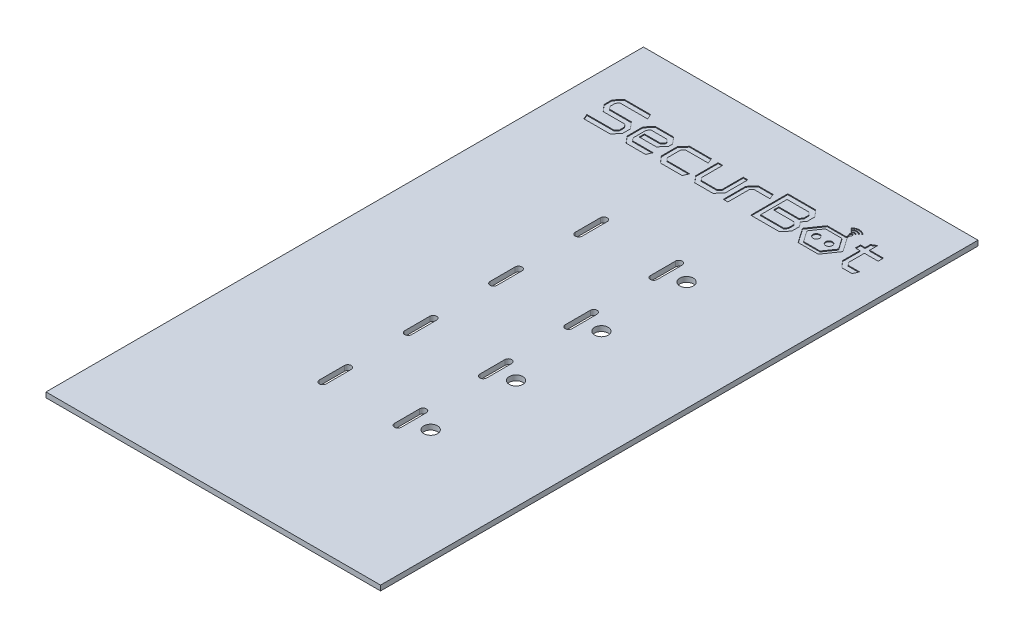
SolidWorks part; units mm, degrees
ref_plane "Front Plane" through (0, 0, 0) normal (0, 0, 1) x (1, 0, 0)
ref_plane "Top Plane" through (0, 0, 0) normal (0, 1, 0) x (1, 0, 0)
ref_plane "Right Plane" through (0, 0, 0) normal (1, 0, 0) x (0, 0, -1)
sketch "Sketch1" plane through (0, 0, 0) normal (0, 1, 0) x (1, 0, 0)
  line L1 (0, 0) -> (196, 0)
  line L2 (0, 0) -> (0, 350)
  line L3 (0, 350) -> (196, 350)
  line L4 (196, 0) -> (196, 350)
  dimension "D1" = 350
  dimension "D2" = 196
extrude "Boss-Extrude1" add sketch "Sketch1" along normal blind 3
hole_wizard "Ø8.0mm Dowel Hole1" positions "Sketch2" profile "Sketch3" hole size "Ø8.0" standard "AS" end condition up to next
sketch "Sketch2" plane through (0, 0, 0) normal (0, -1, 0) x (-1, 0, 0)
  point P0 (-131.875, 93.5)
  point P3 (-131.875, 143.5)
  point P6 (-131.875, 193.5067)
  point P9 (-131.875, 243.4059)
sketch "Sketch3" plane through (131.875, 0, -93.5) normal (1, 0, 0) x (0, 0, -1)
  line L0 (0, 0) -> (0, 3)
  line L1 (0, 3) -> (4, 3)
  line L2 (4, 3) -> (4, 0)
  line L5 (4, 0) -> (0, 0)
  line L11 (0, -6.35) -> (0, 107.95) construction
  dimension "Thru Hole Dia." = 8
  dimension "Thru Hole Depth" = 3
hole_wizard "Ø4.0mm Dowel Slot1" positions "Sketch4" profile "Sketch5" size "Ø4.0" standard "AS" slot yes end condition up to next
sketch "Sketch4" plane through (0, 0, 0) normal (0, -1, 0) x (-1, 0, 0)
  line L0 (-120, 84.15) -> (-120, 102.85) construction
  point P0 (-120, 93.5)
  point P7 (-76, 93.5)
  point P10 (-120, 143.5)
  point P13 (-76, 143.5)
  point P16 (-120, 193.5067)
  point P19 (-76, 193.5067)
  point P22 (-120, 243.4059)
  point P25 (-76, 243.4059)
  dimension "D1" = 18.7
sketch "Sketch5" plane through (120, 0, -93.5) normal (1, 0, 0) x (0, 0, -1)
  line L0 (0, 0) -> (0, 3)
  line L1 (0, 3) -> (2, 3)
  line L2 (2, 3) -> (2, 0)
  line L5 (2, 0) -> (0, 0)
  line L11 (0, -6.35) -> (0, 107.95) construction
  dimension "Thru Hole Dia." = 4
  dimension "Thru Hole Depth" = 3
sketch "Sketch12" plane through (0, 3, 0) normal (0, 1, 0) x (1, 0, 0)
  line L0 (0, 350) -> (0, 300)
  line L1 (0, 350) -> (0, 0) construction
  line L2 (0, 300) -> (98, 300)
sketch "Sketch14" plane through (0, 3, 0) normal (0, 1, 0) x (1, 0, 0)
  line L0 (141.5351, 300.3658) -> (138.5775, 304.6298)
  line L1 (138.5775, 304.6298) -> (141.5351, 308.8937)
  line L2 (141.5351, 308.8937) -> (144.4926, 313.1577)
  line L3 (144.4926, 313.1577) -> (150.0965, 313.1588)
  line L4 (150.0965, 313.1588) -> (155.7003, 313.1599)
  line L5 (155.7003, 313.1599) -> (155.7003, 313.9708)
  line L6 (155.7003, 313.9708) -> (155.7003, 314.7817)
  line L7 (155.7003, 314.7817) -> (155.57, 314.8651)
  line L8 (156.4983, 314.8744) -> (156.3797, 314.8004)
  line L9 (156.3797, 314.8004) -> (156.3787, 313.9527)
  line L10 (156.3787, 313.9527) -> (156.3777, 313.105)
  line L11 (156.3777, 313.105) -> (159.3193, 308.8674)
  line L12 (159.3193, 308.8674) -> (162.261, 304.6298)
  line L13 (162.261, 304.6298) -> (159.3035, 300.3658)
  line L14 (159.3035, 300.3658) -> (156.3459, 296.1018)
  line L15 (156.3459, 296.1018) -> (150.4193, 296.1018)
  line L16 (150.4193, 296.1018) -> (144.4926, 296.1018)
  line L17 (144.4926, 296.1018) -> (141.5351, 300.3658)
  line L18 (157.4604, 307.8365) -> (155.2414, 311.0327)
  line L19 (155.2414, 311.0327) -> (150.4192, 311.0327)
  line L20 (150.4192, 311.0327) -> (145.5971, 311.0327)
  line L21 (145.5971, 311.0327) -> (143.378, 307.8365)
  line L22 (145.4176, 298.4861) -> (145.6066, 298.2162)
  line L23 (145.6066, 298.2162) -> (150.424, 298.2215)
  line L24 (150.424, 298.2215) -> (155.2415, 298.2269)
  line L25 (155.2415, 298.2269) -> (157.4604, 301.423)
  line L26 (25.6857, 299.2375) -> (33.7249, 299.2429)
  line L27 (33.7249, 299.2429) -> (34.3863, 300.0049)
  line L28 (34.3863, 300.0049) -> (35.0477, 300.7669)
  line L29 (35.0477, 300.7669) -> (35.0485, 302.3226)
  line L30 (35.0485, 302.3226) -> (35.0494, 303.8784)
  line L31 (35.0494, 303.8784) -> (34.3778, 304.656)
  line L32 (34.3778, 304.656) -> (33.7062, 305.4336)
  line L33 (33.7062, 305.4336) -> (27.3432, 305.4338)
  line L34 (27.3432, 305.4338) -> (20.9802, 305.4341)
  line L35 (20.9802, 305.4341) -> (19.3052, 307.3737)
  line L36 (19.3052, 307.3737) -> (17.6302, 309.3133)
  line L37 (17.6302, 309.3133) -> (17.6302, 311.6337)
  line L38 (17.6302, 311.6337) -> (17.6302, 313.954)
  line L39 (17.6302, 313.954) -> (19.3065, 315.8959)
  line L40 (19.3065, 315.8959) -> (20.9828, 317.8378)
  line L41 (20.9828, 317.8378) -> (28.6882, 317.8325)
  line L42 (28.6882, 317.8325) -> (36.3936, 317.8272)
  line L43 (36.3936, 317.8272) -> (37.0555, 316.2944)
  line L44 (29.6793, 314.7255) -> (21.6412, 314.7247)
  line L45 (21.6412, 314.7247) -> (20.9802, 313.9582)
  line L46 (20.9802, 313.9582) -> (20.3192, 313.1917)
  line L47 (20.3192, 313.1917) -> (20.3188, 311.6359)
  line L48 (20.3188, 311.6359) -> (20.3183, 310.0801)
  line L49 (20.3183, 310.0801) -> (20.9891, 309.3022)
  line L50 (20.9891, 309.3022) -> (21.6598, 308.5244)
  line L51 (21.6598, 308.5244) -> (28.0228, 308.5244)
  line L52 (28.0228, 308.5244) -> (34.3859, 308.5244)
  line L53 (34.3859, 308.5244) -> (36.0622, 306.5825)
  line L54 (36.0622, 306.5825) -> (37.7385, 304.6405)
  line L55 (37.7385, 304.6405) -> (37.7385, 302.3289)
  line L56 (37.7385, 302.3289) -> (37.7385, 300.0173)
  line L57 (37.7385, 300.0173) -> (37.5956, 299.8478)
  line L58 (35.9182, 297.9002) -> (34.3836, 296.1221)
  line L59 (34.3836, 296.1221) -> (26.6789, 296.1216)
  line L60 (26.6789, 296.1216) -> (18.9742, 296.1211)
  line L61 (18.9742, 296.1211) -> (18.3212, 297.6349)
  line L62 (42.0618, 298.0628) -> (40.3846, 300.0049)
  line L63 (40.3846, 300.0049) -> (40.3844, 304.6529)
  line L64 (40.3844, 304.6529) -> (40.3841, 309.3009)
  line L65 (40.3841, 309.3009) -> (42.0596, 311.241)
  line L66 (42.0596, 311.241) -> (43.7351, 313.1811)
  line L67 (43.7351, 313.1811) -> (49.0967, 313.1811)
  line L68 (49.0967, 313.1811) -> (54.4583, 313.1811)
  line L69 (54.4583, 313.1811) -> (56.1313, 311.2435)
  line L70 (56.1313, 311.2435) -> (57.8043, 309.3058)
  line L71 (57.8043, 309.3058) -> (57.8043, 308.1436)
  line L72 (57.8043, 308.1436) -> (57.8043, 306.9814)
  line L73 (57.8043, 306.9814) -> (56.1313, 305.0436)
  line L74 (56.1313, 305.0436) -> (54.4585, 303.1058)
  line L75 (54.4585, 303.1058) -> (49.4323, 303.1058)
  line L76 (49.4323, 303.1058) -> (44.406, 303.1058)
  line L77 (44.406, 303.1058) -> (44.406, 304.6509)
  line L78 (44.406, 304.6509) -> (44.406, 306.1961)
  line L79 (44.406, 306.1961) -> (49.0917, 306.1961)
  line L80 (49.0917, 306.1961) -> (53.7773, 306.1961)
  line L81 (53.7773, 306.1961) -> (54.4468, 306.9717)
  line L82 (54.4468, 306.9717) -> (55.1163, 307.7472)
  line L83 (55.1163, 307.7472) -> (55.1163, 308.1432)
  line L84 (55.1163, 308.1432) -> (55.1163, 308.5392)
  line L85 (55.1163, 308.5392) -> (54.4476, 309.315)
  line L86 (54.4476, 309.315) -> (53.7788, 310.0908)
  line L87 (53.7788, 310.0908) -> (49.0969, 310.0908)
  line L88 (49.0969, 310.0908) -> (44.4149, 310.0908)
  line L89 (44.4149, 310.0908) -> (43.7438, 309.3129)
  line L90 (43.7438, 309.3129) -> (43.0727, 308.535)
  line L91 (43.0727, 308.535) -> (43.0733, 304.6509)
  line L92 (43.0733, 304.6509) -> (43.0738, 300.7669)
  line L93 (43.0738, 300.7669) -> (43.7346, 300.0005)
  line L94 (43.7346, 300.0005) -> (44.3954, 299.2341)
  line L95 (44.3954, 299.2341) -> (50.4251, 299.2332)
  line L96 (55.781, 297.6394) -> (55.1269, 296.1217)
  line L97 (55.1269, 296.1217) -> (49.4329, 296.1212)
  line L98 (49.4329, 296.1212) -> (43.739, 296.1208)
  line L99 (43.739, 296.1208) -> (42.0618, 298.0628)
  line L100 (62.1701, 298.0628) -> (60.4929, 300.0049)
  line L101 (60.4929, 300.0049) -> (60.4927, 304.6529)
  line L102 (60.4927, 304.6529) -> (60.4925, 309.3009)
  line L103 (60.4925, 309.3009) -> (62.168, 311.241)
  line L104 (62.168, 311.241) -> (63.8435, 313.1811)
  line L105 (63.8435, 313.1811) -> (70.2086, 313.1811)
  line L106 (70.2086, 313.1811) -> (76.5737, 313.1811)
  line L107 (76.5737, 313.1811) -> (76.9094, 312.4032)
  line L108 (77.5745, 310.8634) -> (77.9041, 310.1014)
  line L109 (77.9041, 310.1014) -> (71.2091, 310.0908)
  line L110 (71.2091, 310.0908) -> (64.5142, 310.0802)
  line L111 (64.5142, 310.0802) -> (63.8475, 309.3076)
  line L112 (63.8475, 309.3076) -> (63.1808, 308.535)
  line L113 (63.1808, 308.535) -> (63.1814, 304.6509)
  line L114 (63.1814, 304.6509) -> (63.1819, 300.7669)
  line L115 (63.1819, 300.7669) -> (63.8428, 300.0005)
  line L116 (63.8428, 300.0005) -> (64.5036, 299.2341)
  line L117 (64.5036, 299.2341) -> (71.1975, 299.2332)
  line L118 (77.232, 297.6501) -> (76.5721, 296.1208)
  line L119 (76.5721, 296.1208) -> (70.2096, 296.1208)
  line L120 (70.2096, 296.1208) -> (63.8471, 296.1208)
  line L121 (63.8471, 296.1208) -> (62.1701, 298.0628)
  line L122 (82.2567, 298.0626) -> (80.5798, 300.0044)
  line L123 (80.5798, 300.0044) -> (80.5798, 306.5928)
  line L124 (80.5798, 306.5928) -> (80.5798, 313.1811)
  line L125 (80.5798, 313.1811) -> (81.9239, 313.1811)
  line L126 (81.9239, 313.1811) -> (83.268, 313.1811)
  line L127 (83.268, 313.1811) -> (83.268, 306.9793)
  line L128 (83.268, 306.9793) -> (83.268, 300.7775)
  line L129 (83.268, 300.7775) -> (83.9367, 300.0048)
  line L130 (83.9367, 300.0048) -> (84.6053, 299.2322)
  line L131 (84.6053, 299.2322) -> (89.2967, 299.2375)
  line L132 (89.2967, 299.2375) -> (93.9881, 299.2429)
  line L133 (93.9881, 299.2429) -> (94.649, 300.0049)
  line L134 (94.649, 300.0049) -> (95.3099, 300.7669)
  line L135 (95.3099, 300.7669) -> (95.3109, 306.974)
  line L136 (95.3109, 306.974) -> (95.3118, 313.1811)
  line L137 (95.3118, 313.1811) -> (96.6559, 313.1811)
  line L138 (96.6559, 313.1811) -> (98, 313.1811)
  line L139 (98, 313.1811) -> (98, 306.5906)
  line L140 (98, 306.5906) -> (98, 300)
  line L141 (98, 300) -> (96.325, 298.0604)
  line L142 (96.325, 298.0604) -> (94.65, 296.1208)
  line L143 (94.65, 296.1208) -> (89.2918, 296.1208)
  line L144 (89.2918, 296.1208) -> (83.9336, 296.1208)
  line L145 (83.9336, 296.1208) -> (82.2567, 298.0626)
  line L146 (100.667, 302.7108) -> (100.667, 309.3009)
  line L147 (100.667, 309.3009) -> (102.3425, 311.2411)
  line L148 (102.3425, 311.2411) -> (104.0181, 313.1812)
  line L149 (104.0181, 313.1812) -> (108.3761, 313.1759)
  line L150 (108.3761, 313.1759) -> (112.7341, 313.1705)
  line L151 (112.7341, 313.1705) -> (113.3969, 311.6359)
  line L152 (113.3969, 311.6359) -> (114.0596, 310.1014)
  line L153 (114.0596, 310.1014) -> (109.3741, 310.0908)
  line L154 (109.3741, 310.0908) -> (104.6887, 310.0802)
  line L155 (104.6887, 310.0802) -> (104.022, 309.3076)
  line L156 (104.022, 309.3076) -> (103.3554, 308.535)
  line L157 (103.3554, 308.535) -> (103.3554, 302.3279)
  line L158 (103.3554, 302.3279) -> (103.3554, 296.1208)
  line L159 (103.3554, 296.1208) -> (102.0113, 296.1208)
  line L160 (102.0113, 296.1208) -> (100.6672, 296.1208)
  line L161 (100.6672, 296.1208) -> (100.667, 302.7108)
  line L162 (116.7325, 306.9793) -> (116.7325, 317.8378)
  line L163 (116.7325, 317.8378) -> (124.9081, 317.8372)
  line L164 (124.9081, 317.8372) -> (133.0837, 317.8366)
  line L165 (133.0837, 317.8366) -> (134.6183, 316.0585)
  line L166 (136.2958, 314.1109) -> (136.4387, 313.9413)
  line L167 (136.4387, 313.9413) -> (136.4387, 311.6294)
  line L168 (136.4387, 311.6294) -> (136.4387, 309.3175)
  line L169 (136.4387, 309.3175) -> (135.5391, 308.2762)
  line L170 (135.7402, 305.9153) -> (136.8408, 304.6411)
  line L171 (136.8408, 304.6411) -> (136.8408, 302.3292)
  line L172 (136.8408, 302.3292) -> (136.8408, 300.0173)
  line L173 (136.8408, 300.0173) -> (136.698, 299.8478)
  line L174 (135.0205, 297.9001) -> (133.4859, 296.122)
  line L175 (133.4859, 296.122) -> (125.1092, 296.1214)
  line L176 (125.1092, 296.1214) -> (116.7325, 296.1208)
  line L177 (116.7325, 296.1208) -> (116.7325, 306.9793)
  line L178 (133.4822, 300.0084) -> (134.1527, 300.7846)
  line L179 (134.1527, 300.7846) -> (134.1527, 302.3332)
  line L180 (134.1527, 302.3332) -> (134.1527, 303.8818)
  line L181 (134.1527, 303.8818) -> (133.4822, 304.658)
  line L182 (133.4822, 304.658) -> (132.8118, 305.4341)
  line L183 (132.8118, 305.4341) -> (126.783, 305.4341)
  line L184 (126.783, 305.4341) -> (120.7542, 305.4341)
  line L185 (120.7542, 305.4341) -> (120.7542, 306.9899)
  line L186 (120.7542, 306.9899) -> (120.7542, 308.5456)
  line L187 (120.7542, 308.5456) -> (126.5819, 308.5456)
  line L188 (126.5819, 308.5456) -> (132.4097, 308.5456)
  line L189 (132.4097, 308.5456) -> (133.0801, 309.3195)
  line L190 (133.0801, 309.3195) -> (133.7505, 310.0934)
  line L191 (133.7505, 310.0934) -> (133.7505, 311.6359)
  line L192 (133.7505, 311.6359) -> (133.7505, 313.1785)
  line L193 (133.7505, 313.1785) -> (133.0801, 313.9524)
  line L194 (133.0801, 313.9524) -> (132.4097, 314.7263)
  line L195 (132.4097, 314.7263) -> (125.9152, 314.7263)
  line L196 (125.9152, 314.7263) -> (119.4207, 314.7263)
  line L197 (119.4207, 314.7263) -> (119.4207, 306.9793)
  line L198 (119.4207, 306.9793) -> (119.4207, 299.2323)
  line L199 (119.4207, 299.2323) -> (126.1162, 299.2323)
  line L200 (126.1162, 299.2323) -> (132.8118, 299.2323)
  line L201 (132.8118, 299.2323) -> (133.4822, 300.0084)
  line L202 (168.3797, 298.0577) -> (166.707, 299.9947)
  line L203 (166.707, 299.9947) -> (166.707, 305.0427)
  line L204 (166.707, 305.0427) -> (166.707, 310.0908)
  line L205 (166.707, 310.0908) -> (165.3629, 310.0908)
  line L206 (165.3629, 310.0908) -> (164.0188, 310.0908)
  line L207 (164.0188, 310.0908) -> (164.0188, 311.6359)
  line L208 (164.0188, 311.6359) -> (164.0188, 313.1811)
  line L209 (164.0188, 313.1811) -> (165.3628, 313.1811)
  line L210 (165.3628, 313.1811) -> (166.7067, 313.1811)
  line L211 (166.7067, 313.1811) -> (166.7122, 314.7383)
  line L212 (166.7122, 314.7383) -> (166.7176, 316.2955)
  line L213 (166.7176, 316.2955) -> (168.0405, 317.062)
  line L214 (168.0405, 317.062) -> (169.3634, 317.8285)
  line L215 (169.3634, 317.8285) -> (169.374, 315.5101)
  line L216 (169.374, 315.5101) -> (169.3846, 313.1917)
  line L217 (169.3846, 313.1917) -> (173.401, 313.1863)
  line L218 (173.401, 313.1863) -> (177.4173, 313.181)
  line L219 (177.4173, 313.181) -> (177.4173, 311.6359)
  line L220 (177.4173, 311.6359) -> (177.4173, 310.0909)
  line L221 (177.4173, 310.0909) -> (173.401, 310.0855)
  line L222 (173.401, 310.0855) -> (169.3846, 310.0802)
  line L223 (169.3846, 310.0802) -> (169.3792, 305.433)
  line L224 (169.3792, 305.433) -> (169.3739, 300.7859)
  line L225 (169.3739, 300.7859) -> (170.0439, 300.0091)
  line L226 (170.0439, 300.0091) -> (170.7139, 299.2323)
  line L227 (170.7139, 299.2323) -> (174.0679, 299.2323)
  line L228 (176.1037, 296.179) -> (176.077, 296.1208)
  line L229 (176.077, 296.1208) -> (173.0647, 296.1208)
  line L230 (173.0647, 296.1208) -> (170.0524, 296.1208)
  line L231 (170.0524, 296.1208) -> (168.3797, 298.0577)
  line L232 (154.6149, 316.8806) -> (154.43, 317.0664)
  line L233 (154.43, 317.0664) -> (154.5519, 317.1695)
  line L234 (157.3633, 316.8879) -> (157.1848, 316.7132)
  line L235 (157.1848, 316.7132) -> (157.0723, 316.8048)
  line L236 (153.5958, 317.8997) -> (153.4111, 318.0853)
  line L237 (153.4111, 318.0853) -> (153.545, 318.2068)
  line L238 (158.5461, 318.1569) -> (158.5873, 318.111)
  line L239 (158.5873, 318.111) -> (158.4043, 317.928)
  line L240 (158.4043, 317.928) -> (158.2213, 317.7449)
  line L241 (158.2213, 317.7449) -> (158.0967, 317.8533)
  line L242 (153.952, 317.8626) -> (153.7806, 317.7141)
  line L243 (153.7806, 317.7141) -> (153.5958, 317.8997)
  line L244 (152.6528, 318.8428) -> (152.4742, 319.0222)
  line L245 (152.4742, 319.0222) -> (152.5368, 319.0884)
  line L246 (159.4985, 319.1096) -> (159.5395, 319.0638)
  line L247 (159.5395, 319.0638) -> (159.3614, 318.8847)
  spline S0 degree 3 poles (155.57, 314.8651) (155.3342, 315.0161) (155.1712, 315.3097) (155.1712, 315.5835) knots 0 0 0 0 1 1 1 1
  spline S1 degree 3 poles (155.1712, 315.5835) (155.1712, 316.1418) (155.7342, 316.5632) (156.2647, 316.4021) knots 0 0 0 0 1 1 1 1
  spline S2 degree 3 poles (156.2647, 316.4021) (156.6262, 316.2923) (156.8857, 315.9503) (156.8857, 315.5839) knots 0 0 0 0 1 1 1 1
  spline S3 degree 3 poles (156.8857, 315.5839) (156.8857, 315.3149) (156.7212, 315.0137) (156.4983, 314.8744) knots 0 0 0 0 1 1 1 1
  spline S4 degree 3 poles (157.4604, 301.423) (158.6809, 303.1809) (159.6794, 304.624) (159.6794, 304.6298) knots 0 0 0 0 1 1 1 1
  spline S5 degree 3 poles (159.6794, 304.6298) (159.6794, 304.6356) (158.6808, 306.0786) (157.4604, 307.8365) knots 0 0 0 0 1 1 1 1
  spline S6 degree 3 poles (143.378, 307.8365) (142.1575, 306.0786) (141.1626, 304.6305) (141.167, 304.6185) knots 0 0 0 0 1 1 1 1
  spline S7 degree 3 poles (141.167, 304.6185) (141.1738, 304.6001) (144.8409, 299.3095) (145.4176, 298.4861) knots 0 0 0 0 1 1 1 1
  spline S8 degree 3 poles (146.4611, 302.6325) (145.9965, 302.706) (145.6379, 302.8809) (145.3216, 303.1881) knots 0 0 0 0 1 1 1 1
  spline S9 degree 3 poles (145.3216, 303.1881) (145.0489, 303.4529) (144.8651, 303.7713) (144.7739, 304.1366) knots 0 0 0 0 1 1 1 1
  spline S10 degree 3 poles (144.7739, 304.1366) (144.7374, 304.2824) (144.7273, 304.3849) (144.7273, 304.6086) knots 0 0 0 0 1 1 1 1
  spline S11 degree 3 poles (144.7273, 304.6086) (144.7273, 305.0332) (144.8186, 305.3491) (145.0426, 305.6999) knots 0 0 0 0 1 1 1 1
  spline S12 degree 3 poles (145.0426, 305.6999) (145.1515, 305.8704) (145.4143, 306.1369) (145.5867, 306.2516) knots 0 0 0 0 1 1 1 1
  spline S13 degree 3 poles (145.5867, 306.2516) (145.9421, 306.4881) (146.2688, 306.5858) (146.7045, 306.5858) knots 0 0 0 0 1 1 1 1
  spline S14 degree 3 poles (146.7045, 306.5858) (147.1291, 306.5858) (147.445, 306.4945) (147.7958, 306.2705) knots 0 0 0 0 1 1 1 1
  spline S15 degree 3 poles (147.7958, 306.2705) (147.9663, 306.1616) (148.2328, 305.8988) (148.3475, 305.7264) knots 0 0 0 0 1 1 1 1
  spline S16 degree 3 poles (148.3475, 305.7264) (148.584, 305.3711) (148.6817, 305.0443) (148.6817, 304.6086) knots 0 0 0 0 1 1 1 1
  spline S17 degree 3 poles (148.6817, 304.6086) (148.6817, 304.3849) (148.6716, 304.2824) (148.6351, 304.1366) knots 0 0 0 0 1 1 1 1
  spline S18 degree 3 poles (148.6351, 304.1366) (148.5439, 303.7713) (148.3601, 303.4529) (148.0874, 303.1881) knots 0 0 0 0 1 1 1 1
  spline S19 degree 3 poles (148.0874, 303.1881) (147.7146, 302.8261) (147.2914, 302.6471) (146.768, 302.6303) knots 0 0 0 0 1 1 1 1
  spline S20 degree 3 poles (146.768, 302.6303) (146.6341, 302.6259) (146.496, 302.6269) (146.4611, 302.6325) knots 0 0 0 0 1 1 1 1
  spline S21 degree 3 poles (153.8694, 302.6325) (153.4049, 302.706) (153.0463, 302.8809) (152.7299, 303.1881) knots 0 0 0 0 1 1 1 1
  spline S22 degree 3 poles (152.7299, 303.1881) (152.4573, 303.4529) (152.2734, 303.7713) (152.1822, 304.1366) knots 0 0 0 0 1 1 1 1
  spline S23 degree 3 poles (152.1822, 304.1366) (152.1458, 304.2824) (152.1357, 304.3849) (152.1357, 304.6086) knots 0 0 0 0 1 1 1 1
  spline S24 degree 3 poles (152.1357, 304.6086) (152.1357, 305.0332) (152.2269, 305.3491) (152.451, 305.6999) knots 0 0 0 0 1 1 1 1
  spline S25 degree 3 poles (152.451, 305.6999) (152.5599, 305.8704) (152.8226, 306.1369) (152.9951, 306.2516) knots 0 0 0 0 1 1 1 1
  spline S26 degree 3 poles (152.9951, 306.2516) (153.3504, 306.4881) (153.6772, 306.5858) (154.1128, 306.5858) knots 0 0 0 0 1 1 1 1
  spline S27 degree 3 poles (154.1128, 306.5858) (154.5492, 306.5858) (154.8748, 306.4883) (155.2325, 306.2505) knots 0 0 0 0 1 1 1 1
  spline S28 degree 3 poles (155.2325, 306.2505) (155.4006, 306.1387) (155.6685, 305.8657) (155.778, 305.6945) knots 0 0 0 0 1 1 1 1
  spline S29 degree 3 poles (155.778, 305.6945) (155.9983, 305.3501) (156.09, 305.031) (156.09, 304.6086) knots 0 0 0 0 1 1 1 1
  spline S30 degree 3 poles (156.09, 304.6086) (156.09, 304.3849) (156.0799, 304.2824) (156.0435, 304.1366) knots 0 0 0 0 1 1 1 1
  spline S31 degree 3 poles (156.0435, 304.1366) (155.9522, 303.7713) (155.7684, 303.4529) (155.4958, 303.1881) knots 0 0 0 0 1 1 1 1
  spline S32 degree 3 poles (155.4958, 303.1881) (155.1229, 302.8261) (154.6998, 302.6471) (154.1763, 302.6303) knots 0 0 0 0 1 1 1 1
  spline S33 degree 3 poles (154.1763, 302.6303) (154.0425, 302.6259) (153.9043, 302.6269) (153.8694, 302.6325) knots 0 0 0 0 1 1 1 1
  spline S34 degree 3 poles (18.3212, 297.6349) (17.9621, 298.4676) (17.6633, 299.1676) (17.6573, 299.1905) knots 0 0 0 0 1 1 1 1
  spline S35 degree 3 poles (17.6573, 299.1905) (17.6465, 299.232) (17.6975, 299.2323) (25.6857, 299.2375) knots 0 0 0 0 1 1 1 1
  spline S36 degree 3 poles (37.0555, 316.2944) (37.4195, 315.4514) (37.7173, 314.7537) (37.7173, 314.7439) knots 0 0 0 0 1 1 1 1
  spline S37 degree 3 poles (37.7173, 314.7439) (37.7173, 314.7342) (34.1002, 314.7259) (29.6793, 314.7255) knots 0 0 0 0 1 1 1 1
  spline S38 degree 3 poles (37.5956, 299.8478) (37.517, 299.7546) (36.7622, 298.8781) (35.9182, 297.9002) knots 0 0 0 0 1 1 1 1
  spline S39 degree 3 poles (50.4251, 299.2332) (56.1869, 299.2323) (56.4544, 299.2306) (56.445, 299.1947) knots 0 0 0 0 1 1 1 1
  spline S40 degree 3 poles (56.445, 299.1947) (56.4396, 299.1741) (56.1408, 298.4742) (55.781, 297.6394) knots 0 0 0 0 1 1 1 1
  spline S41 degree 3 poles (76.9094, 312.4032) (77.094, 311.9754) (77.3933, 311.2825) (77.5745, 310.8634) knots 0 0 0 0 1 1 1 1
  spline S42 degree 3 poles (71.1975, 299.2332) (76.538, 299.2325) (77.8915, 299.2269) (77.8917, 299.2058) knots 0 0 0 0 1 1 1 1
  spline S43 degree 3 poles (77.8917, 299.2058) (77.8917, 299.1913) (77.5949, 298.4912) (77.232, 297.6501) knots 0 0 0 0 1 1 1 1
  spline S44 degree 3 poles (134.6183, 316.0585) (135.4624, 315.0806) (136.2172, 314.2041) (136.2958, 314.1109) knots 0 0 0 0 1 1 1 1
  spline S45 degree 3 poles (135.5391, 308.2762) (135.0443, 307.7034) (134.6395, 307.2246) (134.6395, 307.2122) knots 0 0 0 0 1 1 1 1
  spline S46 degree 3 poles (134.6395, 307.2122) (134.6395, 307.1997) (135.1348, 306.6161) (135.7402, 305.9153) knots 0 0 0 0 1 1 1 1
  spline S47 degree 3 poles (136.698, 299.8478) (136.6194, 299.7546) (135.8645, 298.8781) (135.0205, 297.9001) knots 0 0 0 0 1 1 1 1
  spline S48 degree 3 poles (174.0679, 299.2323) (176.7426, 299.2323) (177.4197, 299.2269) (177.4113, 299.2058) knots 0 0 0 0 1 1 1 1
  spline S49 degree 3 poles (177.4113, 299.2058) (177.393, 299.1598) (176.1316, 296.2399) (176.1037, 296.179) knots 0 0 0 0 1 1 1 1
  spline S50 degree 3 poles (154.5519, 317.1695) (154.8096, 317.3874) (155.1268, 317.5518) (155.4631, 317.6415) knots 0 0 0 0 1 1 1 1
  spline S51 degree 3 poles (155.4631, 317.6415) (155.6435, 317.6896) (155.7099, 317.6963) (156.0072, 317.6963) knots 0 0 0 0 1 1 1 1
  spline S52 degree 3 poles (156.0072, 317.6963) (156.3046, 317.6963) (156.371, 317.6896) (156.5514, 317.6415) knots 0 0 0 0 1 1 1 1
  spline S53 degree 3 poles (156.5514, 317.6415) (156.7924, 317.5772) (157.0642, 317.4544) (157.2627, 317.3202) knots 0 0 0 0 1 1 1 1
  spline S54 degree 3 poles (157.2627, 317.3202) (157.4154, 317.217) (157.5418, 317.1082) (157.5418, 317.08) knots 0 0 0 0 1 1 1 1
  spline S55 degree 3 poles (157.5418, 317.08) (157.5418, 317.0704) (157.4615, 316.9839) (157.3633, 316.8879) knots 0 0 0 0 1 1 1 1
  spline S56 degree 3 poles (157.0723, 316.8048) (156.4481, 317.3127) (155.5054, 317.3021) (154.9126, 316.7803) knots 0 0 0 0 1 1 1 1
  spline S57 degree 3 poles (154.9126, 316.7803) (154.8592, 316.7333) (154.8119, 316.6948) (154.8076, 316.6948) knots 0 0 0 0 1 1 1 1
  spline S58 degree 3 poles (154.8076, 316.6948) (154.8034, 316.6948) (154.7166, 316.7784) (154.6149, 316.8806) knots 0 0 0 0 1 1 1 1
  spline S59 degree 3 poles (153.545, 318.2068) (154.1378, 318.7447) (154.84, 319.0596) (155.6474, 319.1497) knots 0 0 0 0 1 1 1 1
  spline S60 degree 3 poles (155.6474, 319.1497) (156.5957, 319.2555) (157.5889, 318.9533) (158.3545, 318.3261) knots 0 0 0 0 1 1 1 1
  spline S61 degree 3 poles (158.3545, 318.3261) (158.4372, 318.2583) (158.5235, 318.1822) (158.5461, 318.1569) knots 0 0 0 0 1 1 1 1
  spline S62 degree 3 poles (158.0967, 317.8533) (157.784, 318.1253) (157.3777, 318.3606) (157.0127, 318.4811) knots 0 0 0 0 1 1 1 1
  spline S63 degree 3 poles (157.0127, 318.4811) (156.6675, 318.5951) (156.4396, 318.629) (156.0178, 318.629) knots 0 0 0 0 1 1 1 1
  spline S64 degree 3 poles (156.0178, 318.629) (155.6913, 318.629) (155.5893, 318.621) (155.404, 318.5813) knots 0 0 0 0 1 1 1 1
  spline S65 degree 3 poles (155.404, 318.5813) (154.8377, 318.4597) (154.379, 318.2327) (153.952, 317.8626) knots 0 0 0 0 1 1 1 1
  spline S66 degree 3 poles (152.5368, 319.0884) (152.5713, 319.1249) (152.6899, 319.2308) (152.8005, 319.3237) knots 0 0 0 0 1 1 1 1
  spline S67 degree 3 poles (152.8005, 319.3237) (153.6923, 320.0736) (154.8706, 320.5046) (156.0284, 320.5046) knots 0 0 0 0 1 1 1 1
  spline S68 degree 3 poles (156.0284, 320.5046) (157.1859, 320.5046) (158.3617, 320.0747) (159.2563, 319.3241) knots 0 0 0 0 1 1 1 1
  spline S69 degree 3 poles (159.2563, 319.3241) (159.3669, 319.2314) (159.4759, 319.1348) (159.4985, 319.1096) knots 0 0 0 0 1 1 1 1
  spline S70 degree 3 poles (159.3614, 318.8847) (159.2634, 318.7862) (159.1782, 318.7059) (159.1721, 318.7064) knots 0 0 0 0 1 1 1 1
  spline S71 degree 3 poles (159.1721, 318.7064) (159.1661, 318.7068) (159.0626, 318.7921) (158.9422, 318.896) knots 0 0 0 0 1 1 1 1
  spline S72 degree 3 poles (158.9422, 318.896) (157.9008, 319.7944) (156.5129, 320.1574) (155.15, 319.8878) knots 0 0 0 0 1 1 1 1
  spline S73 degree 3 poles (155.15, 319.8878) (154.3768, 319.7348) (153.7019, 319.4029) (153.0851, 318.8721) knots 0 0 0 0 1 1 1 1
  spline S74 degree 3 poles (153.0851, 318.8721) (152.9516, 318.7573) (152.8399, 318.6633) (152.8368, 318.6633) knots 0 0 0 0 1 1 1 1
  spline S75 degree 3 poles (152.8368, 318.6633) (152.8338, 318.6633) (152.751, 318.744) (152.6528, 318.8428) knots 0 0 0 0 1 1 1 1
extrude "Cut-Extrude2" cut sketch "Sketch14" against normal blind 0.5 contours S38 L57 L56 L55 L54 L53 L52 L51 L50 L49 L48 L47 L46 L45 L44 S37 S36 L43 L42 L41 L40 L39 L38 L37 L36 L35 L34 L33 L32 L31 L30 L29 L28 L27 L26 S35 S34 L61 L60 L59 L58 | S40 S39 L95 L94 L93 L92 L91 L90 L89 L88 L87 L86 L85 L84 L83 L82 L81 L80 L79 L78 L77 L76 L75 L74 L73 L72 L71 L70 L69 L68 L67 L66 L65 L64 L63 L62 L99 L98 L97 L96 | S43 S42 L117 L116 L115 L114 L113 L112 L111 L110 L109 L108 S41 L107 L106 L105 L104 L103 L102 L101 L100 L121 L120 L119 L118 | L145 L144 L143 L142 L141 L140 L139 L138 L137 L136 L135 L134 L133 L132 L131 L130 L129 L128 L127 L126 L125 L124 L123 L122 | L161 L160 L159 L158 L157 L156 L155 L154 L153 L152 L151 L150 L149 L148 L147 L146 | S47 L173 L172 L171 L170 S46 S45 L169 L168 L167 L166 S44 L165 L164 L163 L162 L177 L176 L175 L174 L201 L200 L199 L198 L197 L196 L195 L194 L193 L192 L191 L190 L189 L188 L187 L186 L185 L184 L183 L182 L181 L180 L179 L178 | S3 S2 S1 S0 L7 L6 L5 L4 L3 L2 L1 L0 L17 L16 L15 L14 L13 L12 L11 L10 L9 L8 S7 S6 L21 L20 L19 L18 S5 S4 L25 L24 L23 L22 | S75 S74 S73 S72 S71 S70 L247 L246 S69 S68 S67 S66 L245 L244 | S65 S64 S63 S62 L241 L240 L239 L238 S61 S60 S59 L237 L236 L243 L242 | S58 S57 S56 L235 L234 S55 S54 S53 S52 S51 S50 L233 L232 | S20 S19 S18 S17 S16 S15 S14 S13 S12 S11 S10 S9 S8 | S33 S32 S31 S30 S29 S28 S27 S26 S25 S24 S23 S22 S21 | S49 S48 L227 L226 L225 L224 L223 L222 L221 L220 L219 L218 L217 L216 L215 L214 L213 L212 L211 L210 L209 L208 L207 L206 L205 L204 L203 L202 L231 L230 L229 L228 region at (140.3128, 3, -302.6757) region at (27.6812, 3, -306.9717) region at (48.4591, 3, -304.9105) region at (61.516, 3, -299.1932) region at (81.6028, 3, -299.1929) region at (100.8839, 3, -306.0059) region at (126.2478, 3, -306.9295) region at (167.7364, 3, -299.1929) region at (155.9928, 3, -317.2636) region at (153.5416, 3, -318.0304) region at (152.6153, 3, -318.984) region at (146.7045, 3, -304.6087) region at (154.1128, 3, -304.6086)
